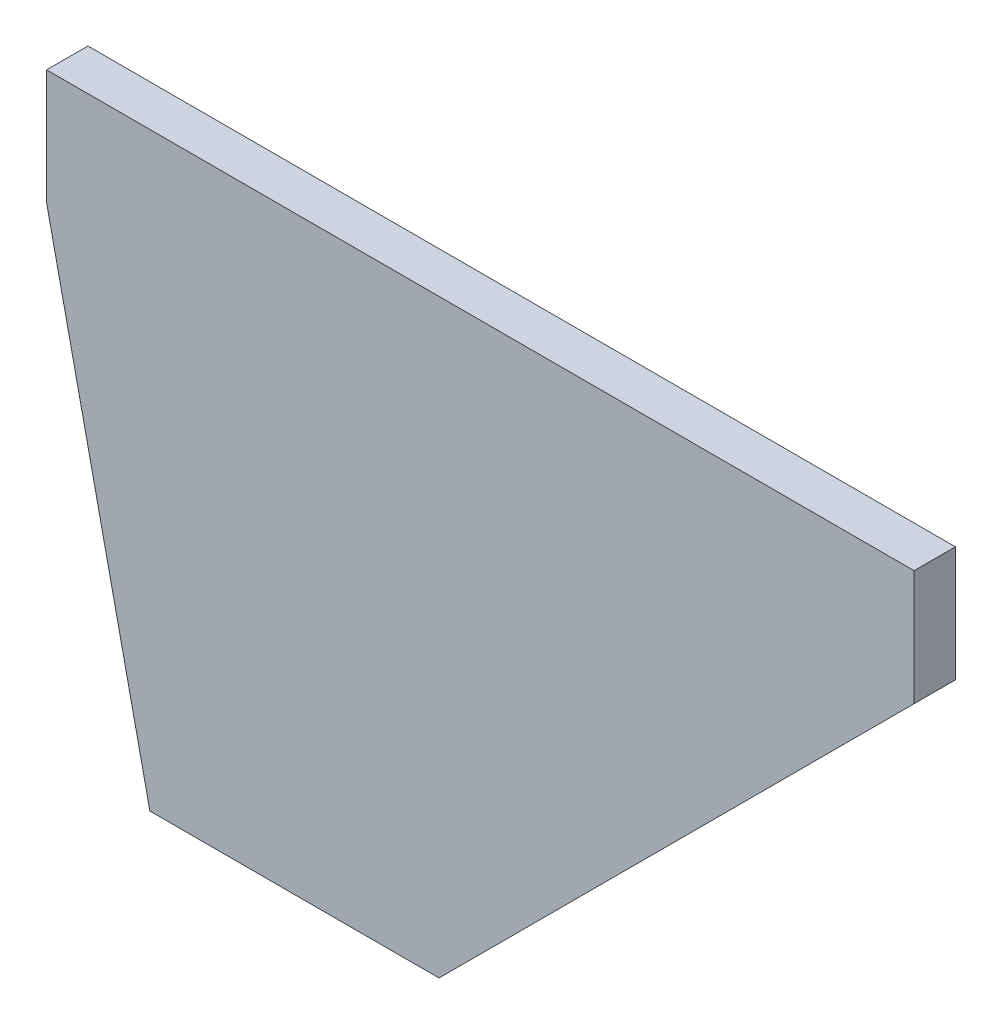
SolidWorks part; units mm, degrees
material "Zoltek Panex 33"
ref_plane "Plan de face" through (0, 0, 0) normal (0, 0, 1) x (1, 0, 0)
ref_plane "Plan de dessus" through (0, 0, 0) normal (0, 1, 0) x (1, 0, 0)
ref_plane "Plan de droite" through (0, 0, 0) normal (1, 0, 0) x (0, 0, -1)
sketch "Esquisse2" plane through (0, 0, 0) normal (0, 0, 1) x (1, 0, 0)
  line L0 (-30.1972, -50.239) -> (-5.1972, -165.239)
  line L1 (-30.1972, -50.239) -> (-30.1972, -22.339)
  line L2 (-30.1972, -22.339) -> (179.8028, -22.339)
  line L3 (179.8028, -22.339) -> (179.8028, -50.239)
  line L4 (179.8028, -50.239) -> (64.8028, -165.239)
  line L5 (64.8028, -165.239) -> (-5.1972, -165.239)
  line L6 (119.8028, -50.239) -> (869.8028, -50.239) construction
  line L7 (-30.1972, -22.339) -> (0, -22.339) construction
  point P0 (179.8028, -50.239)
  point P10 (0, 0)
  dimension "D1" = 210
  dimension "D2" = 70
  dimension "D3" = 45
  dimension "D4" = 115
extrude "Boss.-Extru.1" add sketch "Esquisse2" along normal mid plane 10
